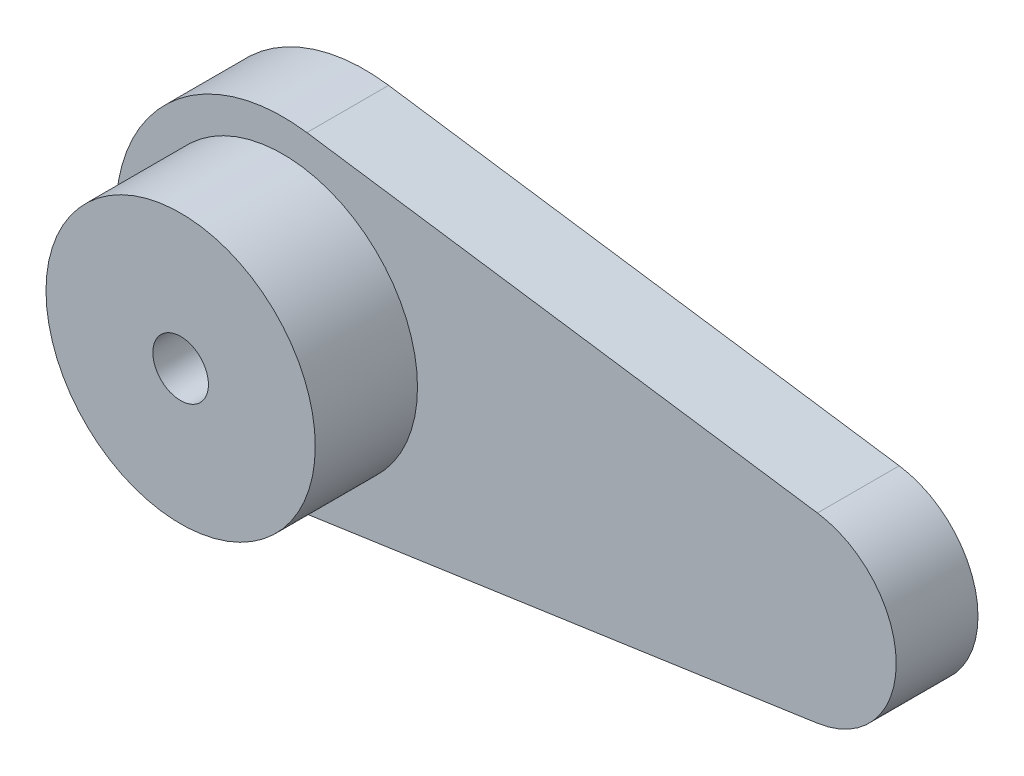
SolidWorks part; units mm, degrees
ref_plane "Front Plane" through (0, 0, 0) normal (0, 0, 1) x (1, 0, 0)
ref_plane "Top Plane" through (0, 0, 0) normal (0, 1, 0) x (1, 0, 0)
ref_plane "Right Plane" through (0, 0, 0) normal (1, 0, 0) x (0, 0, -1)
sketch "Sketch1" plane through (0, 0, 0) normal (0, 0, 1) x (1, 0, 0)
  line L0 (1.1735, 8.0802) -> (26.1468, 4.4533)
  line L3 (1.1735, -8.0802) -> (26.1468, -4.4533)
  arc A2 (1.1735, 8.0802) -> (1.1735, -8.0802) centre (0, 0) ccw
  arc A3 (26.1468, 4.4533) -> (26.1468, -4.4533) centre (25.5, 0) cw
  point P1 (30, 0)
  dimension "D1" = 16.33
  dimension "D3" = 4.5
  dimension "D2" = 30
extrude "Boss-Extrude3" add sketch "Sketch1" along normal blind 5
sketch "Sketch3" plane through (0, 0, 5) normal (0, 0, 1) x (1, 0, 0)
  circle A0 centre (0, 0) radius 6.585
  dimension "D1" = 13.17
extrude "Boss-Extrude4" add sketch "Sketch3" along normal blind 5
sketch "Sketch5" plane through (0, 0, 0) normal (0, 0, -1) x (-1, 0, 0)
  circle A0 centre (0, 0) radius 4.185
  dimension "D1" = 8.37
extrude "Cut-Extrude1" cut sketch "Sketch5" against normal blind 7.5
sketch "Sketch4" plane through (0, 0, 0) normal (0, 0, -1) x (-1, 0, 0)
  line L1 (-1.02, 4.185) -> (1.02, 4.185)
  line L2 (-1.02, 4.185) -> (-1.02, 3.165)
  line L3 (-1.02, 3.165) -> (1.02, 3.165)
  line L4 (1.02, 4.185) -> (1.02, 3.165)
  line L16 (4.185, 1.02) -> (3.165, 1.02)
  line L17 (4.185, 1.02) -> (4.185, -1.02)
  line L18 (4.185, -1.02) -> (3.165, -1.02)
  line L19 (3.165, 1.02) -> (3.165, -1.02)
  line L20 (1.02, -4.185) -> (1.02, -3.165)
  line L21 (1.02, -4.185) -> (-1.02, -4.185)
  line L22 (-1.02, -4.185) -> (-1.02, -3.165)
  line L23 (1.02, -3.165) -> (-1.02, -3.165)
  line L24 (-4.185, -1.02) -> (-3.165, -1.02)
  line L25 (-4.185, -1.02) -> (-4.185, 1.02)
  line L26 (-4.185, 1.02) -> (-3.165, 1.02)
  line L27 (-3.165, -1.02) -> (-3.165, 1.02)
  circle A0 centre (0, 0) radius 4.185 construction
  circle A2 centre (0, 0) radius 4.185 construction
  point P7 (0, 4.185)
  point P23 (0, 0)
  point P26 (0, 0)
  dimension "D2" = 2.04
  dimension "D3" = 1.02
  dimension "D1" = 4
extrude "Boss-Extrude5" add sketch "Sketch4" against normal up to surface (7.5 mm away) up to face at (-4.185, 0, 7.5)
sketch "Sketch6" plane through (0, 0, 10) normal (0, 0, 1) x (1, 0, 0)
  circle A0 centre (0, 0) radius 1.36
  dimension "D1" = 2.72
extrude "Cut-Extrude2" cut sketch "Sketch6" against normal up to surface (2.5 mm away) up to face at (0, 0, 7.5)
sketch "Sketch7" plane through (0, 0, 0) normal (0, 0, -1) x (-1, 0, 0)
  line L0 (-26.1468, 4.4533) -> (-1.1735, 8.0802)
  line L1 (-26.1468, -4.4533) -> (-1.1735, -8.0802)
  arc A0 (-1.1735, -8.0802) -> (-1.1735, 8.0802) centre (0, 0) ccw
  circle A1 centre (0, 0) radius 6.585
  arc A2 (-26.1468, 4.4533) -> (-26.1468, -4.4533) centre (-25.5, 0) ccw
  dimension "D1" = 13.17
  dimension "D2" = 16.33
extrude "Cut-Extrude3" cut sketch "Sketch7" against normal blind 1
fillet "Fillet1" radius 0.5 1 edges at (-6.585, 0, 0)
equation "\"handle_length\"=30.00"
equation "\"key_width\"=2.04"
equation "\"bore_diameter\"=8.37"
equation "\"screw_diameter\"=2.72"
equation "\"handle_width\"=16.33"
equation "\"D1@Sketch1\"=\"handle_width\""
equation "\"extrude_diameter\"=13.17"
equation "\"D1@Sketch3\"=\"extrude_diameter\""
equation "\"D1@Sketch5\"=\"bore_diameter\""
equation "\"D2@Sketch4\"=\"key_width\""
equation "\"D3@Sketch4\"=\"key_length\""
equation "\"D1@Sketch6\"=\"screw_diameter\""
equation "\"D2@Sketch7\"=\"handle_width\""
equation "\"D1@Sketch7\"=\"extrude_diameter\""
equation "\"key_length\"=1.02"
equation "\"D2@Sketch1\"=\"handle_length\""
